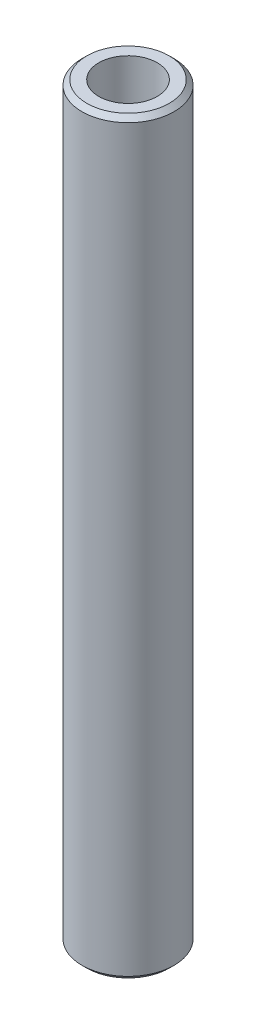
SolidWorks part; units mm, degrees
ref_plane "Front Plane" through (0, 0, 0) normal (0, 0, 1) x (1, 0, 0)
ref_plane "Top Plane" through (0, 0, 0) normal (0, 1, 0) x (1, 0, 0)
ref_plane "Right Plane" through (0, 0, 0) normal (1, 0, 0) x (0, 0, -1)
sketch "Sketch1" plane through (0, 0, 0) normal (0, 1, 0) x (1, 0, 0)
  circle A0 centre (0, 0) radius 25
  dimension "SHAFT_OD" = 50
extrude "Boss-Extrude1" add sketch "Sketch1" along normal blind 406.7836
sketch "Sketch2" plane through (0, 0, 0) normal (0, 1, 0) x (1, 0, 0)
  circle A0 centre (0, 0) radius 15.8856
  dimension "BORE_D" = 31.7712
extrude "Cut-Extrude1" cut sketch "Sketch2" along normal through all
chamfer "Chamfer1" distance 2.6162 angle 45 2 edges at (0, 406.7836, 25) (0, 0, 25)
